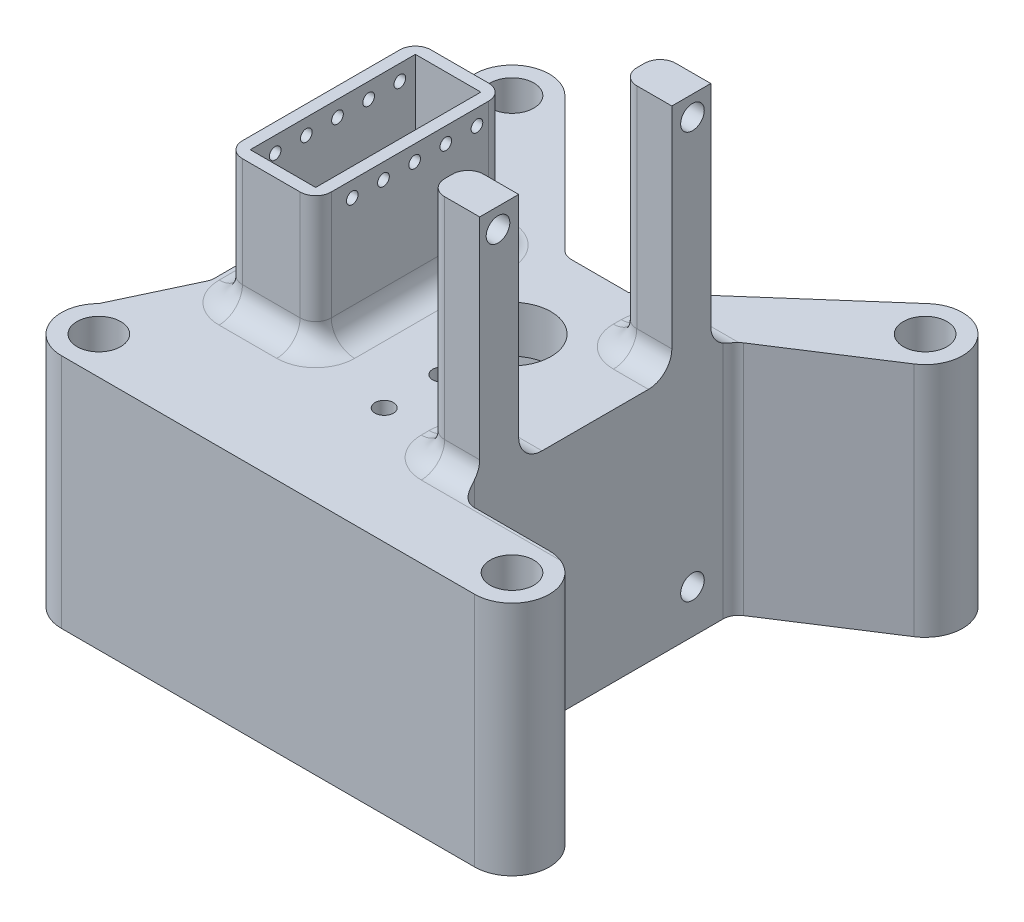
SolidWorks part; units mm, degrees
ref_plane "Front Plane" through (0, 0, 0) normal (0, 0, 1) x (1, 0, 0)
ref_plane "Top Plane" through (0, 0, 0) normal (0, 1, 0) x (1, 0, 0)
ref_plane "Right Plane" through (0, 0, 0) normal (1, 0, 0) x (0, 0, -1)
sketch "Sketch3" plane through (0, 0, 0) normal (0, 1, 0) x (1, 0, 0)
  line L0 (-33.676, -39.772) -> (33.676, -39.772)
  line L1 (-33.676, -33.676) -> (33.676, -33.676) construction
  line L2 (-33.676, -33.676) -> (-33.676, 33.676) construction
  line L3 (-33.676, 33.676) -> (33.676, 33.676) construction
  line L4 (33.676, -33.676) -> (33.676, 33.676) construction
  line L5 (-33.676, -33.676) -> (33.676, 33.676) construction
  line L6 (-33.676, 33.676) -> (33.676, -33.676) construction
  line L7 (10.033, -30.099) -> (-10.033, -30.099)
  line L8 (10.033, -30.099) -> (10.033, 10.033)
  line L9 (10.033, 10.033) -> (3.556, 10.033)
  line L10 (-10.033, -30.099) -> (-10.033, 10.033)
  line L11 (10.033, -30.099) -> (-10.033, 10.033) construction
  line L12 (10.033, 10.033) -> (-10.033, -30.099) construction
  line L13 (33.676, -27.58) -> (18.923, -27.58)
  line L14 (-3.556, 15.367) -> (3.556, 15.367) construction
  line L15 (-3.556, 15.367) -> (-3.556, 10.033)
  line L16 (0, 10.033) -> (3.556, 10.033) construction
  line L17 (3.556, 15.367) -> (3.556, 10.033)
  line L18 (-3.556, 15.367) -> (3.556, 10.033) construction
  line L19 (-3.556, 10.033) -> (3.556, 15.367) construction
  line L20 (-25.781, 10.033) -> (-15.113, 10.033) construction
  line L21 (-25.781, 10.033) -> (-25.781, -16.891) construction
  line L22 (-25.781, -16.891) -> (-15.113, -16.891) construction
  line L23 (-15.113, 10.033) -> (-15.113, -16.891) construction
  line L24 (-25.781, 10.033) -> (-15.113, -16.891) construction
  line L25 (-25.781, -16.891) -> (-15.113, 10.033) construction
  line L26 (18.923, -27.58) -> (18.923, 16.87)
  line L27 (36.9874, 28.5578) -> (18.923, 16.87)
  line L28 (29.6563, 38.259) -> (3.556, 15.367)
  line L31 (0, 10.033) -> (-3.556, 10.033) construction
  line L32 (-29.3669, 37.9879) -> (-6.731, 15.367)
  line L33 (-6.731, 15.367) -> (-3.556, 15.367)
  line L34 (-3.556, 10.033) -> (-10.033, 10.033)
  line L35 (-3.556, 10.033) -> (0, 10.033) construction
  line L36 (3.556, 10.033) -> (0, 10.033) construction
  line L37 (-32.131, -16.891) -> (-32.131, 10.033)
  line L38 (34.003, -24.1637) -> (18.923, -24.1637) construction
  line L39 (34.003, -24.1637) -> (34.003, 13.4537) construction
  line L40 (34.003, 13.4537) -> (18.923, 13.4537) construction
  line L41 (18.923, -24.1637) -> (18.923, 13.4537) construction
  line L42 (34.003, -24.1637) -> (18.923, 13.4537) construction
  line L43 (34.003, 13.4537) -> (18.923, -24.1637) construction
  line L44 (-32.131, 10.033) -> (-39.4519, 31.7268)
  line L45 (-32.131, -16.891) -> (-37.9865, -29.3654)
  circle A0 centre (-33.676, 33.676) radius 3.556
  circle A1 centre (33.676, 33.676) radius 3.556
  circle A2 centre (33.676, -33.676) radius 3.556
  circle A3 centre (-33.676, -33.676) radius 3.556
  circle A4 centre (0, 0) radius 6.35 construction
  circle A5 centre (0, 0) radius 10.033 construction
  circle A6 centre (0, 0) radius 63.5 construction
  arc A7 (33.676, -39.772) -> (33.676, -27.58) centre (33.676, -33.676) ccw
  arc A8 (-39.772, -33.676) -> (-33.676, -39.772) centre (-33.676, -33.676) ccw
  arc A9 (-29.3669, 37.9879) -> (-39.772, 33.676) centre (-33.676, 33.676) ccw
  arc A10 (36.9874, 28.5578) -> (29.6563, 38.259) centre (33.676, 33.676) ccw
  arc A11 (27.58, 33.676) -> (29.3654, 29.3654) centre (33.676, 33.676) ccw construction
  arc A12 (29.6563, 38.259) -> (27.58, 33.676) centre (33.676, 33.676) ccw construction
  arc A13 (29.3654, 29.3654) -> (33.676, 27.58) centre (33.676, 33.676) ccw construction
  arc A14 (33.676, 27.58) -> (36.9874, 28.5578) centre (33.676, 33.676) ccw construction
  arc A15 (-27.58, 33.676) -> (-29.3669, 37.9879) centre (-33.676, 33.676) ccw construction
  arc A16 (-29.3654, 29.3654) -> (-27.58, 33.676) centre (-33.676, 33.676) ccw construction
  arc A17 (-33.676, 27.58) -> (-29.3654, 29.3654) centre (-33.676, 33.676) ccw construction
  arc A18 (-39.772, 33.676) -> (-39.4519, 31.7268) centre (-33.676, 33.676) ccw
  arc A19 (-37.9865, -29.3654) -> (-39.772, -33.676) centre (-33.676, -33.676) ccw
  arc A20 (-29.3654, -29.3654) -> (-33.676, -27.58) centre (-33.676, -33.676) ccw construction
  arc A21 (-27.58, -33.676) -> (-29.3654, -29.3654) centre (-33.676, -33.676) ccw construction
  arc A22 (-33.676, -39.772) -> (-27.58, -33.676) centre (-33.676, -33.676) ccw construction
  arc A23 (33.676, -27.58) -> (29.3654, -29.3654) centre (33.676, -33.676) ccw construction
  arc A24 (29.3654, -29.3654) -> (27.58, -33.676) centre (33.676, -33.676) ccw construction
  arc A25 (27.58, -33.676) -> (33.676, -39.772) centre (33.676, -33.676) ccw construction
  arc A26 (-39.4519, 31.7268) -> (-33.676, 27.58) centre (-33.676, 33.676) ccw construction
  arc A27 (-33.676, -27.58) -> (-37.9865, -29.3654) centre (-33.676, -33.676) ccw construction
  point P0 (0, 0)
  point P10 (0, -10.033)
  point P25 (0, 12.7)
  point P30 (3.556, 12.7)
  point P32 (-20.447, -3.429)
  point P41 (-32.131, 16.87)
  point P53 (18.923, -5.355)
  point P55 (26.463, -5.355)
  point P61 (0, 0)
  point P64 (-32.131, -3.429)
  point P65 (-38.0251, -29.3654)
  point P67 (0, 0)
  dimension "D2" = 7.112
  dimension "D5" = 12.7
  dimension "D6" = 127
  dimension "D1" = 95.25
  dimension "D3" = 40.132
  dimension "D4" = 20.066
  dimension "D7" = 2.54
  dimension "D8" = 5.334
  dimension "D9" = 7.112
  dimension "D10" = 10.668
  dimension "D11" = 26.924
  dimension "D12" = 5.08
  dimension "D13" = 8.89
  dimension "D14" = 171.65
  dimension "D15" = 352.506
  dimension "D16" = 44.45
  dimension "D17" = 37.6174
  dimension "D18" = 3.175
  dimension "D19" = 30.16
  dimension "D21" = 6.35
  dimension "D20" = 67.3519
extrude "Boss-Extrude1" add sketch "Sketch3" along normal blind 21.463
sketch "Sketch4" plane through (0, 21.463, 0) normal (0, 1, 0) x (1, 0, 0)
  line L0 (-3.556, 15.367) -> (3.556, 15.367) construction
  line L1 (-3.556, 10.033) -> (3.556, 10.033) construction
  line L2 (3.556, 15.367) -> (-3.556, 15.367)
  line L3 (-3.556, 10.033) -> (3.556, 10.033)
  line L16 (-10.033, 10.033) -> (-3.556, 10.033)
  line L17 (-3.556, 10.033) -> (-3.556, 15.367)
  line L18 (-3.556, 15.367) -> (-6.731, 15.367)
  line L19 (-6.731, 15.367) -> (-29.3669, 37.9879)
  line L20 (-39.4519, 31.7268) -> (-32.131, 10.033)
  line L21 (-33.676, -39.772) -> (33.676, -39.772)
  line L22 (33.676, -27.58) -> (18.923, -27.58)
  line L23 (18.923, -27.58) -> (18.923, 16.87)
  line L24 (18.923, 16.87) -> (36.9874, 28.5578)
  line L25 (29.6563, 38.259) -> (3.556, 15.367)
  line L27 (3.556, 15.367) -> (3.556, 10.033)
  line L28 (3.556, 10.033) -> (10.033, 10.033)
  line L29 (10.033, 10.033) -> (10.033, -30.099)
  line L30 (10.033, -30.099) -> (-10.033, -30.099)
  line L31 (-10.033, -30.099) -> (-10.033, 10.033)
  line L32 (-10.033, 10.033) -> (-3.556, 10.033)
  line L33 (-3.556, 10.033) -> (-3.556, 15.367) construction
  line L34 (-3.556, 15.367) -> (-6.731, 15.367)
  line L35 (-6.731, 15.367) -> (-29.3669, 37.9879)
  line L37 (-33.676, -39.772) -> (33.676, -39.772)
  line L38 (33.676, -27.58) -> (18.923, -27.58)
  line L39 (18.923, -27.58) -> (18.923, 16.87)
  line L40 (18.923, 16.87) -> (36.9874, 28.5578)
  line L41 (29.6563, 38.259) -> (3.556, 15.367)
  line L43 (3.556, 15.367) -> (3.556, 10.033) construction
  line L44 (3.556, 10.033) -> (10.033, 10.033)
  line L45 (10.033, 10.033) -> (10.033, -30.099)
  line L46 (10.033, -30.099) -> (-10.033, -30.099)
  line L47 (-10.033, -30.099) -> (-10.033, 10.033)
  line L52 (-39.4519, 31.7268) -> (-32.131, 10.033)
  line L53 (-32.131, 10.033) -> (-32.131, -16.891)
  line L54 (-32.131, 10.033) -> (-32.131, -16.891)
  line L55 (-32.131, -16.891) -> (-37.9865, -29.3654)
  line L56 (-32.131, -16.891) -> (-37.9865, -29.3654)
  circle A3 centre (33.676, -33.676) radius 3.556 construction
  arc A4 (-29.3669, 37.9879) -> (-39.4519, 31.7268) centre (-33.676, 33.676) ccw
  arc A5 (-37.9865, -29.3654) -> (-33.676, -39.772) centre (-33.676, -33.676) ccw
  arc A6 (33.676, -39.772) -> (33.676, -27.58) centre (33.676, -33.676) ccw
  arc A7 (36.9874, 28.5578) -> (29.6563, 38.259) centre (33.676, 33.676) ccw
  arc A8 (-29.3669, 37.9879) -> (-39.4519, 31.7268) centre (-33.676, 33.676) ccw
  arc A9 (-37.9865, -29.3654) -> (-33.676, -39.772) centre (-33.676, -33.676) ccw
  arc A10 (33.676, -39.772) -> (33.676, -27.58) centre (33.676, -33.676) ccw
  arc A11 (36.9874, 28.5578) -> (29.6563, 38.259) centre (33.676, 33.676) ccw
  circle A12 centre (33.676, -33.676) radius 3.556
  circle A13 centre (33.676, 33.676) radius 3.556 construction
  circle A14 centre (33.676, 33.676) radius 3.556
  circle A15 centre (-33.676, 33.676) radius 3.556 construction
  circle A16 centre (-33.676, 33.676) radius 3.556
  circle A17 centre (-33.676, -33.676) radius 3.556 construction
  circle A18 centre (-33.676, -33.676) radius 3.556
  dimension "D1" = 0
extrude "Boss-Extrude2" add sketch "Sketch4" along normal blind 7.366
sketch "Sketch5" plane through (0, 28.829, 0) normal (0, 1, 0) x (1, 0, 0)
  line L8 (3.556, 15.367) -> (-6.731, 15.367)
  line L9 (-6.731, 15.367) -> (-29.3669, 37.9879)
  line L10 (-39.4519, 31.7268) -> (-32.131, 10.033)
  line L11 (-33.676, -39.772) -> (33.676, -39.772)
  line L12 (33.676, -27.58) -> (18.923, -27.58)
  line L13 (18.923, -27.58) -> (18.923, 16.87)
  line L14 (18.923, 16.87) -> (36.9874, 28.5578)
  line L15 (29.6563, 38.259) -> (3.556, 15.367)
  line L16 (3.556, 15.367) -> (-6.731, 15.367)
  line L17 (-6.731, 15.367) -> (-29.3669, 37.9879)
  line L19 (-33.676, -39.772) -> (33.676, -39.772)
  line L20 (33.676, -27.58) -> (18.923, -27.58)
  line L21 (18.923, -27.58) -> (18.923, 16.87)
  line L22 (18.923, 16.87) -> (36.9874, 28.5578)
  line L23 (29.6563, 38.259) -> (3.556, 15.367)
  line L26 (-39.4519, 31.7268) -> (-32.131, 10.033)
  line L27 (-32.131, 10.033) -> (-32.131, -16.891)
  line L28 (-32.131, 10.033) -> (-32.131, -16.891)
  line L29 (-32.131, -16.891) -> (-37.9865, -29.3654)
  line L30 (-32.131, -16.891) -> (-37.9865, -29.3654)
  circle A0 centre (0, 0) radius 6.35 construction
  circle A1 centre (33.676, 33.676) radius 3.556
  circle A2 centre (33.676, 33.676) radius 3.556
  circle A3 centre (-33.676, 33.676) radius 3.556
  circle A4 centre (-33.676, 33.676) radius 3.556
  circle A5 centre (-33.676, -33.676) radius 3.556
  circle A6 centre (-33.676, -33.676) radius 3.556
  circle A7 centre (33.676, -33.676) radius 3.556
  circle A8 centre (33.676, -33.676) radius 3.556
  circle A9 centre (0, 0) radius 6.35
  arc A12 (-29.3669, 37.9879) -> (-39.4519, 31.7268) centre (-33.676, 33.676) ccw
  arc A13 (-37.9865, -29.3654) -> (-33.676, -39.772) centre (-33.676, -33.676) ccw
  arc A14 (33.676, -39.772) -> (33.676, -27.58) centre (33.676, -33.676) ccw
  arc A15 (36.9874, 28.5578) -> (29.6563, 38.259) centre (33.676, 33.676) ccw
  arc A16 (-29.3669, 37.9879) -> (-39.4519, 31.7268) centre (-33.676, 33.676) ccw
  arc A17 (-37.9865, -29.3654) -> (-33.676, -39.772) centre (-33.676, -33.676) ccw
  arc A18 (33.676, -39.772) -> (33.676, -27.58) centre (33.676, -33.676) ccw
  arc A19 (36.9874, 28.5578) -> (29.6563, 38.259) centre (33.676, 33.676) ccw
  dimension "D1" = 0
  dimension "D2" = 0
  dimension "D3" = 0
  dimension "D4" = 0
  dimension "D5" = 0
extrude "Boss-Extrude3" add sketch "Sketch5" along normal blind 7.62
sketch "Sketch6" plane through (0, 36.449, 0) normal (0, 1, 0) x (1, 0, 0)
  line L0 (-25.781, 10.033) -> (-25.781, -16.891) construction
  line L1 (-25.781, -16.891) -> (-15.113, -16.891) construction
  line L2 (-15.113, 10.033) -> (-15.113, -16.891) construction
  line L3 (-25.781, 10.033) -> (-15.113, 10.033) construction
  line L4 (-25.781, 10.033) -> (-25.781, -16.891) construction
  line L5 (-25.781, -16.891) -> (-15.113, -16.891) construction
  line L6 (-15.113, 10.033) -> (-15.113, -16.891) construction
  line L7 (-25.781, 10.033) -> (-15.113, 10.033) construction
  line L9 (-13.208, 11.938) -> (-27.686, 11.938)
  line L10 (-13.208, 11.938) -> (-13.208, -18.796)
  line L11 (-13.208, -18.796) -> (-27.686, -18.796)
  line L12 (-27.686, 11.938) -> (-27.686, -18.796)
  line L13 (-13.208, 11.938) -> (-27.686, -18.796) construction
  line L14 (-13.208, -18.796) -> (-27.686, 11.938) construction
  point P4 (-20.447, -3.429)
  point P9 (0, 0)
  point P11 (-20.447, -16.891)
  dimension "D1" = 1.905
  dimension "D2" = 1.905
extrude "Boss-Extrude4" add sketch "Sketch6" along normal blind 21.59
sketch "Sketch7" plane through (0, 58.039, 0) normal (0, 1, 0) x (1, 0, 0)
  line L0 (-25.781, 10.033) -> (-25.781, -16.891) construction
  line L1 (-25.781, -16.891) -> (-15.113, -16.891) construction
  line L2 (-15.113, 10.033) -> (-15.113, -16.891) construction
  line L3 (-25.781, 10.033) -> (-15.113, 10.033) construction
  line L4 (-25.781, 10.033) -> (-25.781, -16.891)
  line L5 (-25.781, -16.891) -> (-15.113, -16.891)
  line L6 (-15.113, 10.033) -> (-15.113, -16.891)
  line L7 (-25.781, 10.033) -> (-15.113, 10.033)
extrude "Cut-Extrude1" cut sketch "Sketch7" against normal blind 50.8
sketch "Sketch8" plane through (-27.686, 0, 0) normal (-1, 0, 0) x (0, 0, 1)
  line L0 (16.891, 7.239) -> (16.891, 58.039) construction
  line L1 (-10.033, 7.239) -> (-10.033, 58.039) construction
  line L2 (16.891, 7.239) -> (16.891, 58.039) construction
  line L3 (-10.033, 7.239) -> (-10.033, 58.039) construction
  line L4 (-7.493, 55.499) -> (-2.413, 55.499) construction
  circle A0 centre (-7.493, 55.499) radius 0.9525
  circle A1 centre (-2.413, 55.499) radius 0.9525
  circle A2 centre (2.667, 55.499) radius 0.9525
  circle A3 centre (7.747, 55.499) radius 0.9525
  circle A4 centre (12.827, 55.499) radius 0.9525
  dimension "D1" = 1.905
  dimension "D5" = 5.08
  dimension "D2" = 2.54
  dimension "D3" = 2.54
  dimension "D4" = 5
extrude "Cut-Extrude2" cut sketch "Sketch8" against normal through all
sketch "Sketch10" plane through (0, 36.449, 0) normal (0, 1, 0) x (1, 0, 0)
  line L0 (18.923, -27.58) -> (18.923, 16.87) construction
  line L1 (10.668, -24.19) -> (18.923, -24.19)
  line L2 (10.668, -24.19) -> (10.668, -17.84)
  line L3 (10.668, 13.48) -> (18.923, 13.48)
  line L4 (18.923, -24.19) -> (18.923, -17.84)
  line L5 (10.668, -24.19) -> (18.923, 13.48) construction
  line L6 (10.668, 13.48) -> (18.923, -24.19) construction
  line L7 (18.923, -27.58) -> (18.923, 16.87) construction
  line L8 (18.923, -17.84) -> (18.923, 7.13) construction
  line L9 (18.923, -17.84) -> (10.668, -17.84)
  line L10 (18.923, -17.84) -> (18.923, 7.13) construction
  line L11 (18.923, 7.13) -> (10.668, 7.13)
  line L12 (10.668, -17.84) -> (10.668, 7.13) construction
  line L13 (18.923, -17.84) -> (10.668, 7.13) construction
  line L14 (18.923, 7.13) -> (10.668, -17.84) construction
  line L15 (18.923, 7.13) -> (18.923, 13.48)
  line L16 (10.668, -17.84) -> (10.668, 7.13) construction
  line L17 (10.668, 7.13) -> (10.668, 13.48)
  point P0 (14.7955, -5.355)
  point P7 (18.923, -5.355)
  point P9 (14.7955, -5.355)
  dimension "D1" = 37.67
  dimension "D2" = 8.255
  dimension "D3" = 6.35
extrude "Boss-Extrude5" add sketch "Sketch10" along normal blind 38.1
sketch "Sketch9" plane through (18.923, 0, 0) normal (1, 0, 0) x (0, 0, -1)
  line L0 (-27.58, 0) -> (16.87, 0) construction
  line L1 (-21.205, 71.3) -> (10.495, 71.3) construction
  line L2 (-21.205, 71.3) -> (-21.205, 5) construction
  line L3 (-21.205, 5) -> (10.495, 5) construction
  line L4 (10.495, 71.3) -> (10.495, 5) construction
  line L5 (-21.205, 71.3) -> (10.495, 5) construction
  line L6 (-21.205, 5) -> (10.495, 71.3) construction
  circle A0 centre (-21.205, 71.3) radius 1.925
  circle A1 centre (10.495, 71.3) radius 1.925
  circle A2 centre (10.495, 5) radius 1.925
  circle A3 centre (-21.205, 5) radius 1.925
  point P0 (-5.355, 38.15)
  dimension "D4" = 3.85
  dimension "D1" = 31.7
  dimension "D2" = 66.3
  dimension "D3" = 5
extrude "Cut-Extrude3" cut sketch "Sketch9" against normal blind 5.75
sketch "Sketch13" plane through (0, 36.449, 0) normal (0, 1, 0) x (1, 0, 0)
  line L0 (0, -11.43) -> (0, -20.828) construction
  circle A0 centre (0, -11.43) radius 1.5
  circle A1 centre (0, -20.828) radius 1.5
  dimension "D2" = 3
  dimension "D1" = 9.398
  dimension "D3" = 11.43
extrude "Cut-Extrude4" cut sketch "Sketch13" against normal blind 4
fillet "Fillet1" radius 2.54 13 edges at (10.668, 55.499, 17.84) (10.668, 55.499, 24.19) (10.668, 55.499, -7.13) (10.668, 55.499, -13.48) (-27.686, 47.244, -11.938) (-13.208, 47.244, -11.938) (-13.208, 47.244, 18.796) (-27.686, 47.244, 18.796) (-32.131, 18.2245, 16.891) (-32.131, 18.2245, -10.033) (-6.731, 18.2245, -15.367) (18.923, 18.2245, -16.87) (18.923, 18.2245, 27.58)
fillet "Fillet2" radius 3.81 18 edges at (-13.9519, 36.449, -11.1941) (-13.208, 36.449, 3.429) (-13.9519, 36.449, 18.0521) (-20.447, 36.449, 18.796) (-26.9421, 36.449, 18.0521) (-27.686, 36.449, 3.429) (-26.9421, 36.449, -11.1941) (16.0655, 36.449, 24.19) (11.4119, 36.449, 23.446) (10.668, 36.449, 21.015) (11.4119, 36.449, 18.5839) (16.0655, 36.449, -7.13) (11.4119, 36.449, -7.874) (10.668, 36.449, -10.305) (11.4119, 36.449, -12.7361) (-20.447, 36.449, -11.938) (16.0655, 36.449, 17.84) (16.0655, 36.449, -13.48)
sketch "Sketch14" plane through (0, 0, 0) normal (0, -1, 0) x (1, 0, 0)
  line L17 (-3.556, -10.033) -> (-10.033, -10.033)
  line L18 (-10.033, -10.033) -> (-10.033, 30.099)
  line L19 (-10.033, 30.099) -> (10.033, 30.099)
  line L20 (10.033, 30.099) -> (10.033, -10.033)
  line L21 (10.033, -10.033) -> (3.556, -10.033)
  line L22 (3.556, -10.033) -> (3.556, -15.367)
  line L23 (3.556, -15.367) -> (29.6563, -38.259)
  line L24 (36.9874, -28.5578) -> (20.0832, -17.6207)
  line L25 (18.923, -15.4881) -> (18.923, 25.04)
  line L26 (21.463, 27.58) -> (33.676, 27.58)
  line L27 (33.676, 39.772) -> (-33.676, 39.772)
  line L28 (-37.9865, 29.3654) -> (-32.3717, 17.4038)
  line L29 (-32.131, 16.3245) -> (-32.131, -9.616)
  line L30 (-32.2643, -10.4281) -> (-39.4519, -31.7268)
  line L31 (-29.3669, -37.9879) -> (-7.4748, -16.1104)
  line L32 (-5.6794, -15.367) -> (-3.556, -15.367)
  line L33 (-3.556, -15.367) -> (-3.556, -10.033)
  line L34 (-3.556, -10.033) -> (-10.033, -10.033)
  line L35 (-10.033, -10.033) -> (-10.033, 30.099)
  line L36 (-10.033, 30.099) -> (10.033, 30.099)
  line L37 (10.033, 30.099) -> (10.033, -10.033)
  line L38 (10.033, -10.033) -> (3.556, -10.033)
  line L39 (3.556, -10.033) -> (3.556, -15.367)
  line L40 (3.556, -15.367) -> (29.6563, -38.259)
  line L41 (36.9874, -28.5578) -> (20.0832, -17.6207)
  line L42 (18.923, -15.4881) -> (18.923, 25.04)
  line L43 (21.463, 27.58) -> (33.676, 27.58)
  line L44 (33.676, 39.772) -> (-33.676, 39.772)
  line L45 (-37.9865, 29.3654) -> (-32.3717, 17.4038)
  line L46 (-32.131, 16.3245) -> (-32.131, -9.616)
  line L47 (-32.2643, -10.4281) -> (-39.4519, -31.7268)
  line L48 (-29.3669, -37.9879) -> (-7.4748, -16.1104)
  line L49 (-5.6794, -15.367) -> (-3.556, -15.367)
  line L50 (-3.556, -15.367) -> (-3.556, -10.033)
  circle A0 centre (-33.676, -33.676) radius 3.556 construction
  circle A1 centre (-33.676, -33.676) radius 3.556
  circle A2 centre (-33.676, 33.676) radius 3.556 construction
  circle A3 centre (-33.676, 33.676) radius 3.556
  circle A4 centre (33.676, 33.676) radius 3.556 construction
  circle A5 centre (33.676, 33.676) radius 3.556
  circle A6 centre (33.676, -33.676) radius 3.556 construction
  circle A7 centre (33.676, -33.676) radius 3.556
  arc A9 (29.6563, -38.259) -> (36.9874, -28.5578) centre (33.676, -33.676) ccw
  arc A10 (18.923, -15.4881) -> (20.0832, -17.6207) centre (21.463, -15.4881) ccw
  arc A11 (21.463, 27.58) -> (18.923, 25.04) centre (21.463, 25.04) ccw
  arc A12 (33.676, 27.58) -> (33.676, 39.772) centre (33.676, 33.676) ccw
  arc A13 (-33.676, 39.772) -> (-37.9865, 29.3654) centre (-33.676, 33.676) ccw
  arc A14 (-32.131, 16.3245) -> (-32.3717, 17.4038) centre (-34.671, 16.3245) ccw
  arc A15 (-32.2643, -10.4281) -> (-32.131, -9.616) centre (-34.671, -9.616) ccw
  arc A16 (-39.4519, -31.7268) -> (-29.3669, -37.9879) centre (-33.676, -33.676) ccw
  arc A17 (-5.6794, -15.367) -> (-7.4748, -16.1104) centre (-5.6794, -17.907) ccw
  arc A18 (29.6563, -38.259) -> (36.9874, -28.5578) centre (33.676, -33.676) ccw
  arc A19 (18.923, -15.4881) -> (20.0832, -17.6207) centre (21.463, -15.4881) ccw
  arc A20 (21.463, 27.58) -> (18.923, 25.04) centre (21.463, 25.04) ccw
  arc A21 (33.676, 27.58) -> (33.676, 39.772) centre (33.676, 33.676) ccw
  arc A22 (-33.676, 39.772) -> (-37.9865, 29.3654) centre (-33.676, 33.676) ccw
  arc A23 (-32.131, 16.3245) -> (-32.3717, 17.4038) centre (-34.671, 16.3245) ccw
  arc A24 (-32.2643, -10.4281) -> (-32.131, -9.616) centre (-34.671, -9.616) ccw
  arc A25 (-39.4519, -31.7268) -> (-29.3669, -37.9879) centre (-33.676, -33.676) ccw
  arc A26 (-5.6794, -15.367) -> (-7.4748, -16.1104) centre (-5.6794, -17.907) ccw
  dimension "D1" = 0
extrude "Boss-Extrude6" add sketch "Sketch14" along normal blind 2.0585
equation "\"AIRFRAME_OD\"= 5.15in"
equation "\"AIRFRAME_ID\"= 5.00in"
equation "\"FLAT_T\"= 0.125in"
equation "\"COUPLER_OD\"= 4.998in"
equation "\"COUPLER_ID\"= 4.88in"
equation "\"NOSE_EXP_L\"= 27in"
equation "\"NOSE_SHOULDER_L\"= 5in"
equation "\"MAIN_L\"= 30in"
equation "\"RECO_COUP_L\"= 10in"
equation "\"RECO_SWITCH_L\"= 2in"
equation "\"RECO_ROD_X\"= 3.5in"
equation "\"DROGUE_L\"= 20in"
equation "\"ATS_FORE_COUP_L\"= 5.5in"
equation "\"ATS_AFT_COUP_L\"= 4.5in"
equation "\"ATS_ROD_X\"= 3.75in"
equation "\"LOWER_L\"= 30in"
equation "\"FIN_ROOT\"= 8in"
equation "\"FIN_X\"= 0.75in"
equation "\"FIN_N\"= 4"
equation "\"MOTOR_OD\"= 3.091in"
equation "\"MOTOR_ID\"= 3.00in"
equation "\"MOTOR_L\"= 14in"
equation "\"CR_AFT_X\"= 0.5in"
equation "\"CR_FORE_X\"= 9.25in"
equation "\"MOTOR_LOWER_X\"= 2in"
equation "\"D1@Sketch3\"=\"ATS_ROD_X\""
equation "\"D6@Sketch3\"=\"AIRFRAME_ID\""
